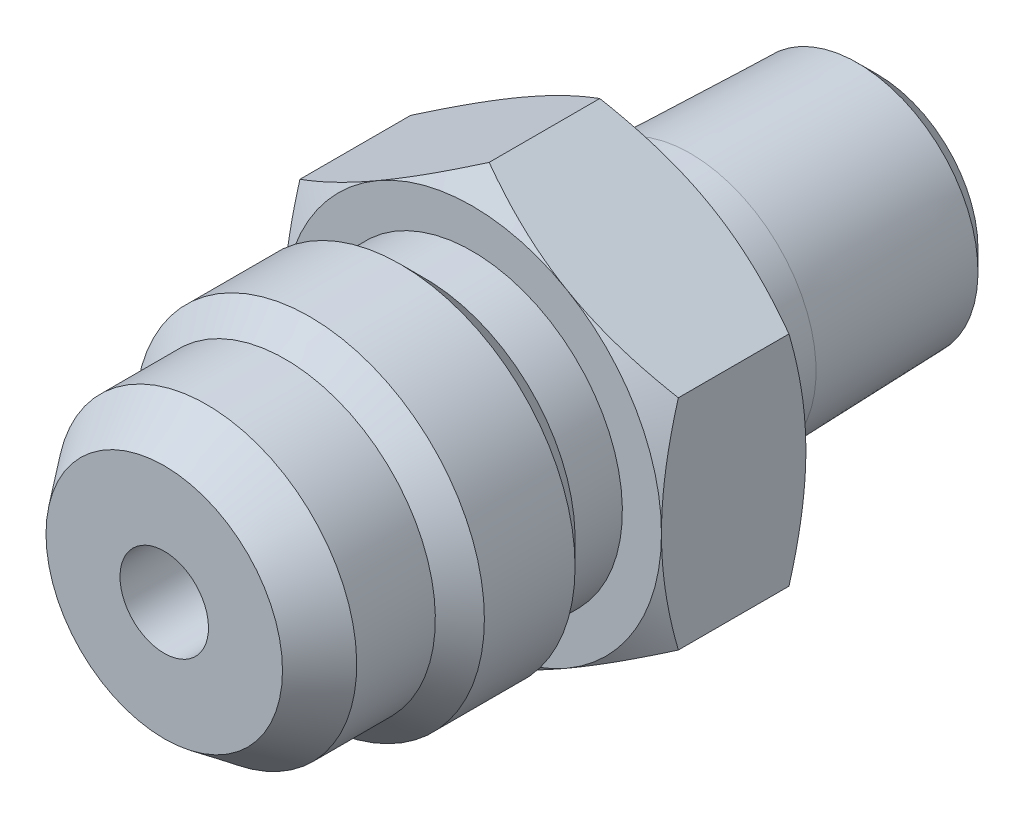
SolidWorks part; units mm, degrees
ref_plane "Front" through (0, 0, 0) normal (0, 0, 1) x (1, 0, 0)
ref_plane "Top" through (0, 0, 0) normal (0, 1, 0) x (1, 0, 0)
ref_plane "Right" through (0, 0, 0) normal (1, 0, 0) x (0, 0, -1)
sketch "Sketch1" plane through (0, 0, 0) normal (1, 0, 0) x (0, 0, -1)
  line L0 (-19.4469, 0) -> (19.4469, 0) construction
  line L1 (-19.4469, 2.413) -> (-19.4469, 6.4481)
  line L2 (-19.4469, 6.4481) -> (-17.1383, 8.1877)
  line L3 (-17.1383, 8.1877) -> (-12.8508, 8.1877)
  line L4 (-12.8508, 8.1877) -> (-11.5135, 9.525)
  line L5 (-11.5135, 9.525) -> (-6.5681, 9.525)
  line L6 (-6.5681, 9.525) -> (-5.2308, 8.1877)
  line L7 (-5.2308, 8.1877) -> (-2.6511, 8.1877)
  line L8 (-19.4469, 6.4481) -> (-18.7873, 6.4481) construction
  line L9 (-18.7873, 6.4481) -> (-18.1277, 6.4481) construction
  line L10 (-2.6511, 8.1877) -> (-2.6511, 10.3187)
  line L11 (-2.6511, 10.3187) -> (5.2229, 10.3187)
  line L12 (5.2229, 10.3187) -> (5.2229, 6.858)
  line L13 (5.2229, 6.858) -> (9.2412, 6.858)
  line L14 (9.2412, 6.858) -> (18.3545, 6.5743)
  line L15 (19.4469, 5.4819) -> (19.4469, 2.413)
  line L16 (19.4469, 2.413) -> (-19.4469, 2.413)
  line L17 (-17.1383, 8.1877) -> (-19.4469, 8.1877) construction
  line L18 (-19.4469, 8.1877) -> (-19.4469, 6.4481) construction
  line L19 (-11.5135, 9.525) -> (-12.8508, 9.525) construction
  line L20 (-12.8508, 9.525) -> (-12.8508, 8.1877) construction
  line L21 (-6.5681, 9.525) -> (-5.2308, 9.525) construction
  line L22 (-5.2308, 9.525) -> (-5.2308, 8.1877) construction
  line L23 (9.2412, 6.858) -> (19.4469, 6.858) construction
  line L24 (18.3545, 6.5743) -> (19.4469, 5.4819)
  line L25 (18.3545, 6.5743) -> (19.4469, 6.5402) construction
  line L26 (19.4469, 5.4819) -> (19.4469, 6.5402) construction
  line L27 (19.4469, 6.5402) -> (19.4469, 6.858) construction
  line L28 (19.4469, 6.5402) -> (19.976, 5.6237) construction
  line L29 (19.976, 5.6237) -> (20.1524, 5.6237) construction
  line L30 (20.1524, 5.6237) -> (20.7549, 6.6672) construction
  line L31 (20.7549, 6.6672) -> (19.3736, 6.6672) construction
  line L32 (19.3736, 6.6672) -> (19.4469, 6.5402) construction
  line L33 (19.7115, 6.082) -> (20.417, 6.082) construction
  line L34 (20.0642, 6.082) -> (20.0642, 5.6237) construction
  line L35 (20.0642, 5.8528) -> (21.4753, 5.8528) construction
  line L36 (-12.8508, 9.525) -> (-19.4469, 9.525) construction
  line L37 (-19.4469, 9.525) -> (-19.4469, 8.1877) construction
  line L38 (-19.4469, 9.525) -> (-20.0422, 8.4939) construction
  line L39 (-20.0422, 8.4939) -> (-20.2406, 8.4939) construction
  line L40 (-20.2406, 8.4939) -> (-20.9093, 9.652) construction
  line L41 (-20.9093, 9.652) -> (-19.3736, 9.652) construction
  line L42 (-19.3736, 9.652) -> (-19.4469, 9.525) construction
  line L43 (-19.7445, 9.0094) -> (-20.5383, 9.0094) construction
  line L44 (-20.1414, 9.0094) -> (-20.1414, 8.4939) construction
  line L45 (-20.1414, 8.7517) -> (-21.7289, 8.7517) construction
  line L46 (-18.1277, 6.4481) -> (-17.4681, 6.4481) construction
  line L47 (-17.4681, 6.4481) -> (-16.8085, 6.4481) construction
  line L48 (-16.8085, 6.4481) -> (-16.1488, 6.4481) construction
  line L49 (-16.1488, 6.4481) -> (-15.4892, 6.4481) construction
  line L50 (-15.4892, 6.4481) -> (-14.8296, 6.4481) construction
  line L51 (-14.8296, 6.4481) -> (-14.17, 6.4481) construction
  line L52 (-14.17, 6.4481) -> (-13.5104, 6.4481) construction
  line L53 (-13.5104, 6.4481) -> (-12.8508, 6.4481) construction
  line L54 (-12.8508, 8.1877) -> (-12.8508, 6.4481) construction
  line L55 (-17.1383, 8.1877) -> (-17.1383, 6.4481) construction
  dimension "D1" = 37
  dimension "D3" = 45
  dimension "D4" = 1.783
  dimension "D2" = 0.127
  dimension "D5" = 60
  dimension "D6" = 0.1764
  dimension "D7" = 0.7056
  dimension "D8" = 1.0583
  dimension "D9" = 0.127
  dimension "D10" = 60
  dimension "D11" = 0.1984
  dimension "D12" = 0.7937
  dimension "D13" = 2.5797
revolve "Revolve1" add sketch "Sketch1" angle 360 about L0
sketch "Sketch2" plane through (0, 0, 2.6511) normal (0, 0, 1) x (1, 0, 0)
  line L1 (0, 11.9151) -> (-10.3188, 5.9575)
  line L2 (-10.3188, 5.9575) -> (-10.3188, -5.9575)
  line L3 (-10.3188, -5.9575) -> (0, -11.9151)
  line L4 (0, -11.9151) -> (10.3188, -5.9575)
  line L5 (10.3188, -5.9575) -> (10.3188, 5.9575)
  line L6 (10.3188, 5.9575) -> (0, 11.9151)
  circle A0 centre (0, 0) radius 10.3187 construction
  circle A1 centre (0, 0) radius 10.3187 construction
  circle A2 centre (0, 0) radius 10.1917
  dimension "D1" = 0.127
extrude "Boss-Extrude1" add sketch "Sketch2" against normal up to surface (7.874 mm away) up to face at (0, -10.3187, -5.2229)
sketch "Sketch3" plane through (0, 0, 0) normal (1, 0, 0) x (0, 0, -1)
  line L0 (-19.4469, 0) -> (19.4469, 0) construction
  line L1 (1.2859, 10.3187) -> (1.2859, 0) construction
  line L2 (-2.6511, 10.3187) -> (5.2229, 10.3187) construction
  line L3 (-2.6511, 10.3187) -> (-2.6511, 11.9151)
  line L4 (-2.6511, 11.9151) -> (-1.7295, 11.9151)
  line L5 (5.2229, 11.9151) -> (-2.6511, 11.9151) construction
  line L6 (-1.7295, 11.9151) -> (-2.6511, 10.3187)
  line L7 (4.3012, 11.9151) -> (5.2229, 10.3187)
  line L8 (5.2229, 11.9151) -> (4.3012, 11.9151)
  line L9 (5.2229, 10.3187) -> (5.2229, 11.9151)
  dimension "D1" = 30
revolve "Cut-Revolve1" cut sketch "Sketch3" angle 360 about L0
sketch "Sketch4" plane through (0, 0, 19.4469) normal (0, 0, 1) x (1, 0, 0)
  circle A0 centre (0, 0) radius 9.525 construction
  circle A1 centre (0, 0) radius 9.525
curve "Helix/Spiral1" pitch 1.5875 height 16.7957 turns 10.58
sketch "Sketch5" [suppressed] plane through (0, 0, 0) normal (1, 0, 0) x (0, 0, -1)
  line L0 (-19.3736, 9.652) -> (-20.0422, 8.4939)
  line L1 (-20.0422, 8.4939) -> (-20.2406, 8.4939)
  line L2 (-20.2406, 8.4939) -> (-20.9093, 9.652)
  line L3 (-20.9093, 9.652) -> (-19.3736, 9.652)
sweep "Sweep1" [suppressed] add profiles "Sketch5" path "Helix/Spiral1"
sketch "Sketch6" [suppressed] plane through (0, 0, -19.4469) normal (0, 0, -1) x (-1, 0, 0)
  circle A0 centre (0, 0) radius 6.5402
curve "Helix/Spiral2" [suppressed]
sketch "Sketch7" [suppressed] plane through (0, 0, 0) normal (1, 0, 0) x (0, 0, -1)
  line L0 (19.3736, 6.6672) -> (19.976, 5.6237)
  line L1 (19.976, 5.6237) -> (20.1524, 5.6237)
  line L2 (20.1524, 5.6237) -> (20.7549, 6.6672)
  line L3 (20.7549, 6.6672) -> (19.3736, 6.6672)
sweep "Sweep2" [suppressed] add profiles "Sketch7" path "Helix/Spiral2"
sketch "Sketch8" [suppressed] plane through (0, 0, 0) normal (1, 0, 0) x (0, 0, -1)
  line L0 (-19.4469, 0) -> (19.4469, 0) construction
  line L1 (-5.2308, -11.9151) -> (9.2412, -11.9151)
  line L2 (-5.2308, -11.9151) -> (-5.2308, 11.9151)
  line L3 (-5.2308, 11.9151) -> (9.2412, 11.9151)
  line L4 (9.2412, -11.9151) -> (9.2412, 11.9151)
  line L5 (-5.2308, -11.9151) -> (9.2412, 11.9151) construction
  line L6 (-5.2308, 11.9151) -> (9.2412, -11.9151) construction
  line L7 (4.3012, 11.9151) -> (-1.7295, 11.9151) construction
  point P0 (2.0052, 0)
extrude "Cut-Extrude1" [suppressed] cut sketch "Sketch8" against normal through all both and the other way through all
combine bodies "Combine1" [suppressed] operation type add bodies to combine 111 114 115
equation "\"D6@Sketch1\"=\"ThreadPitch2@Sketch1\"*.125"
equation "\"D7@Sketch1\"=\"ThreadPitch2@Sketch1\"*.5"
equation "\"D8@Sketch1\"=\"ThreadPitch2@Sketch1\"*.75"
equation "\"D11@Sketch1\"=\"ThreadPitch1@Sketch1\"*.125"
equation "\"D12@Sketch1\"=\"ThreadPitch1@Sketch1\"*.5"
equation "\"D4@Helix/Spiral1\"=\"ThreadPitch1@Sketch1\""
equation "\"D3@Helix/Spiral1\"=\"Length@Sketch1\"-(\"HexWidth@Sketch1\"+\"SideLength2@Sketch1\")"
equation "\"D4@Helix/Spiral2\"=\"ThreadPitch2@Sketch1\""
equation "\"D3@Helix/Spiral2\"=\"ThreadFTE2@Sketch1\"+\"ThreadPitch2@Sketch1\""
equation "\"D13@Sketch1\"=\"ThreadPitch1@Sketch1\"*1.625"
